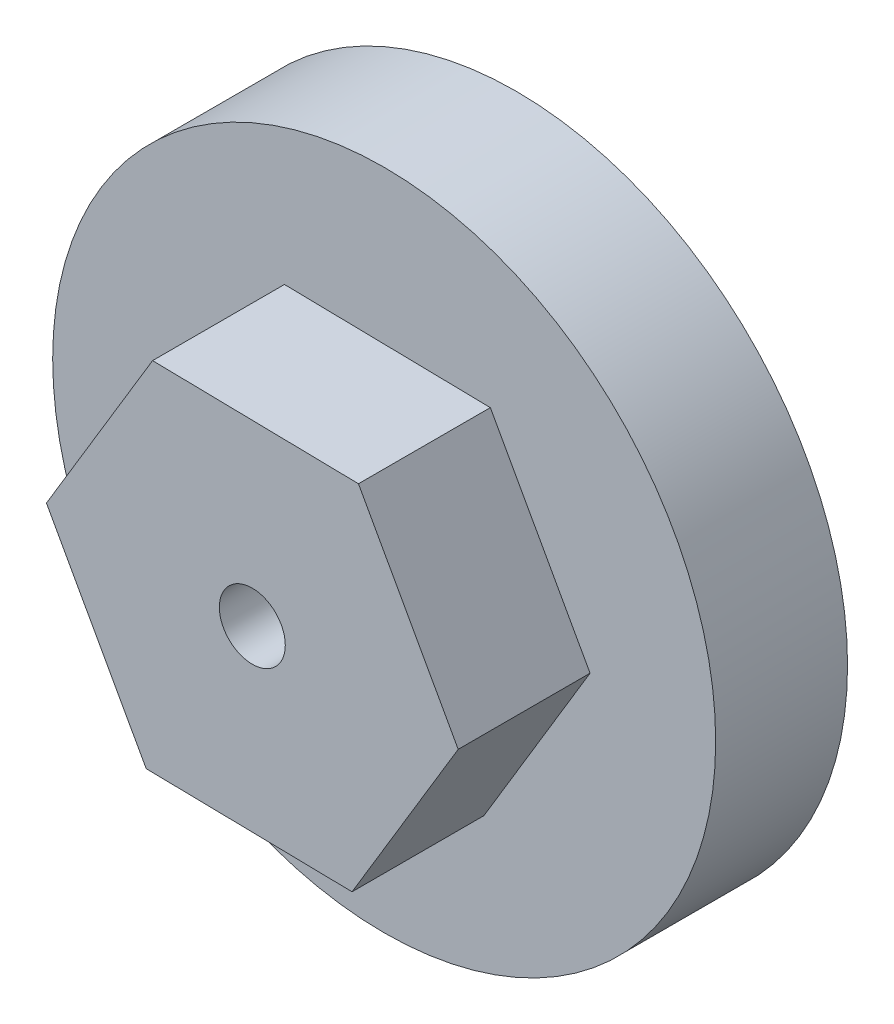
SolidWorks part; units mm, degrees
ref_plane "Front" through (0, 0, 0) normal (0, 0, 1) x (1, 0, 0)
ref_plane "Top" through (0, 0, 0) normal (0, 1, 0) x (1, 0, 0)
ref_plane "Right" through (0, 0, 0) normal (1, 0, 0) x (0, 0, -1)
sketch "Sketch1" plane through (0, 0, 0) normal (0, 0, 1) x (1, 0, 0)
  line L1 (8.0491, 13.3802) -> (-7.563, 13.6608)
  line L2 (-7.563, 13.6608) -> (-15.6121, 0.2806)
  line L3 (-15.6121, 0.2806) -> (-8.0491, -13.3802)
  line L4 (-8.0491, -13.3802) -> (7.563, -13.6608)
  line L5 (7.563, -13.6608) -> (15.6121, -0.2806)
  line L6 (15.6121, -0.2806) -> (8.0491, 13.3802)
  circle A0 centre (0, 0) radius 13.5227 construction
  circle A1 centre (0, 0) radius 25.1393
  circle A2 centre (0, 0) radius 2.5
  circle A3 centre (0, 0) radius 2.5 construction
extrude "Boss-Extrude1" add sketch "Sketch1" along normal blind 10 contours A1 L6 L5 L4 L3 L2 L1 region at (-24.4283, 0, 0)
extrude "Boss-Extrude2" add sketch "Sketch1<3>" along normal blind 20 contours L5 L6 L1 L2 L3 L4 A2 region at (11.4676, 6.3488, 0)
sketch "Sketch1<3>" plane through (0, 0, 0) normal (0, 0, 1) x (1, 0, 0) same geometry as "Sketch1"
